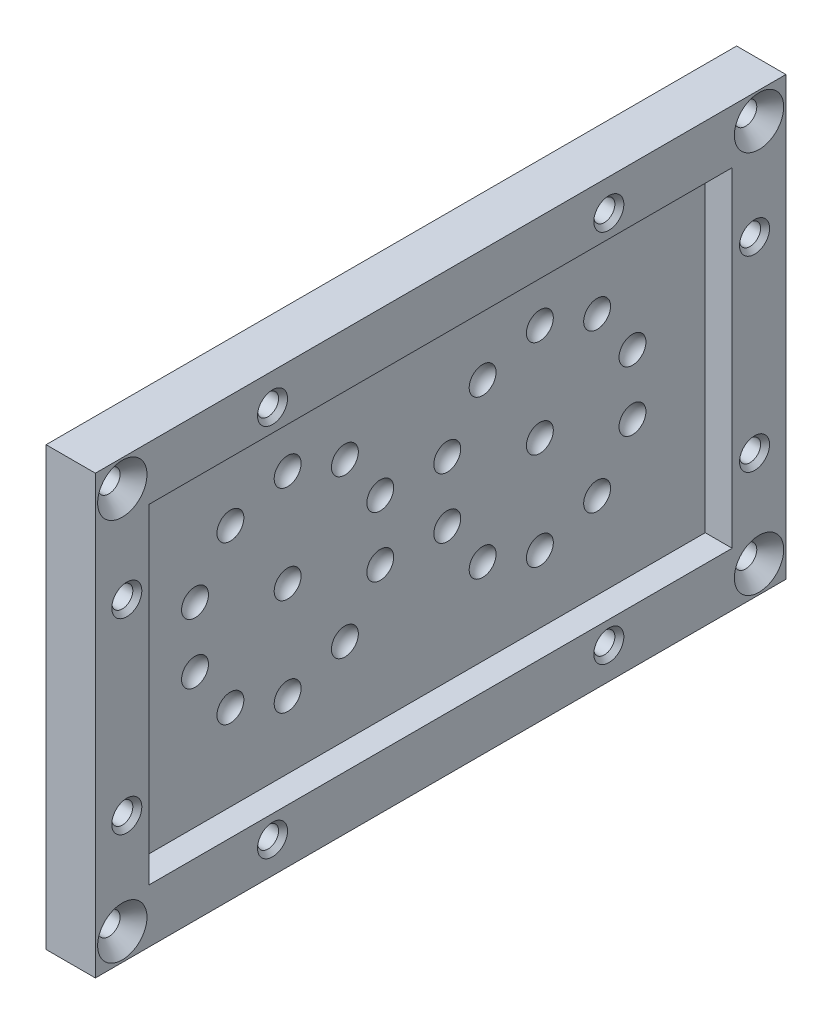
SolidWorks part; units mm, degrees
ref_plane "Front Plane" through (0, 0, 0) normal (0, 0, 1) x (1, 0, 0)
ref_plane "Top Plane" through (0, 0, 0) normal (0, 1, 0) x (1, 0, 0)
ref_plane "Right Plane" through (0, 0, 0) normal (1, 0, 0) x (0, 0, -1)
sketch "Sketch1" plane through (0, 0, 0) normal (1, 0, 0) x (0, 0, -1)
  line L1 (-65, 36.75) -> (65, 36.75)
  line L2 (-65, 36.75) -> (-65, -36.75)
  line L3 (-65, -36.75) -> (65, -36.75)
  line L4 (65, 36.75) -> (65, -36.75)
  line L5 (-65, 36.75) -> (65, -36.75) construction
  line L6 (-65, -36.75) -> (65, 36.75) construction
  point P0 (0, 0)
  dimension "D1" = 130
  dimension "D2" = 73.5
extrude "Boss-Extrude1" add sketch "Sketch1" along normal blind 5 contours L2 L1 L4 L3
sketch "Sketch2" plane through (5, 0, 0) normal (1, 0, 0) x (0, 0, -1)
  line L0 (0, 0) -> (56.25, 0) construction
  line L1 (0, 0) -> (0, 14.8929) construction
  line L12 (-57.5, -29.25) -> (57.5, -29.25) construction
  line L13 (57.5, -29.25) -> (57.5, 29.25) construction
  line L14 (57.5, 29.25) -> (-57.5, 29.25) construction
  line L15 (-57.5, 29.25) -> (-57.5, -29.25) construction
  circle A22 centre (28.125, 0) radius 21.718 construction
  circle A23 centre (28.125, -21.718) radius 3
  circle A24 centre (15.3595, -17.5702) radius 3
  circle A25 centre (7.47, -6.7112) radius 3
  circle A26 centre (7.47, 6.7112) radius 3
  circle A27 centre (15.3595, 17.5702) radius 3
  circle A28 centre (28.125, 21.718) radius 3
  circle A29 centre (40.8905, 17.5702) radius 3
  circle A30 centre (48.78, 6.7112) radius 3
  circle A31 centre (48.78, -6.7112) radius 3
  circle A32 centre (40.8905, -17.5702) radius 3
  circle A33 centre (-7.47, -6.7112) radius 3
  circle A34 centre (-15.3595, -17.5702) radius 3
  circle A35 centre (-28.125, -21.718) radius 3
  circle A36 centre (-40.8905, -17.5702) radius 3
  circle A37 centre (-48.78, -6.7112) radius 3
  circle A38 centre (-48.78, 6.7112) radius 3
  circle A39 centre (-40.8905, 17.5702) radius 3
  circle A40 centre (-28.125, 21.718) radius 3
  circle A41 centre (-15.3595, 17.5702) radius 3
  circle A42 centre (-7.47, 6.7112) radius 3
  circle A43 centre (28.125, 0) radius 3
  circle A44 centre (-28.125, 0) radius 3
  point P31 (28.125, 0)
  dimension "D2" = 43.436
  dimension "D3" = 6
  dimension "D4" = 10
  dimension "D5" = 6
  dimension "D1" = 56.25
extrude "Cut-Extrude1" cut sketch "Sketch2" against normal blind 2
fillet "Fillet1" radius 3.23 22 edges at (3, -6.7112, -10.47) (3, -17.5702, -18.3595) (3, -21.718, -31.125) (3, -17.5702, -43.8905) (3, -6.7112, -51.78) (3, 6.7112, -51.78) (3, 17.5702, -43.8905) (3, 21.718, -31.125) (3, 17.5702, -18.3595) (3, 6.7112, -10.47) (3, 17.5702, 43.8905) (3, 6.7112, 51.78) (3, -6.7112, 51.78) (3, -17.5702, 43.8905) (3, -21.718, 31.125) (3, -17.5702, 18.3595) (3, -6.7112, 10.47) (3, 6.7112, 10.47) (3, 17.5702, 18.3595) (3, 21.718, 31.125) (3, 0, -31.125) (3, 0, 31.125)
sketch "Sketch3" plane through (0, 0, 0) normal (-1, 0, 0) x (0, 0, 1)
  line L1 (-65, -36.75) -> (-75, -36.75)
  line L2 (-65, -36.75) -> (-65, 36.75)
  line L3 (-65, 36.75) -> (-75, 36.75)
  line L4 (-75, -36.75) -> (-75, 36.75)
  line L5 (-65, -36.75) -> (-75, 36.75) construction
  line L6 (-65, 36.75) -> (-75, -36.75) construction
  line L7 (65, -36.75) -> (75, -36.75)
  line L8 (65, -36.75) -> (65, 36.75)
  line L9 (65, 36.75) -> (75, 36.75)
  line L10 (75, -36.75) -> (75, 36.75)
  line L11 (65, -36.75) -> (75, 36.75) construction
  line L12 (65, 36.75) -> (75, -36.75) construction
  line L13 (75, -36.75) -> (-75, -36.75)
  line L14 (75, -36.75) -> (75, -46.75)
  line L15 (75, -46.75) -> (-75, -46.75)
  line L16 (-75, -36.75) -> (-75, -46.75)
  line L17 (75, -36.75) -> (-75, -46.75) construction
  line L18 (75, -46.75) -> (-75, -36.75) construction
  line L19 (-75, 36.75) -> (75, 36.75)
  line L20 (-75, 36.75) -> (-75, 46.75)
  line L21 (-75, 46.75) -> (75, 46.75)
  line L22 (75, 36.75) -> (75, 46.75)
  line L23 (-75, 36.75) -> (75, 46.75) construction
  line L24 (-75, 46.75) -> (75, 36.75) construction
  point P4 (-70, 0)
  point P10 (70, 0)
  point P14 (0, -41.75)
  point P17 (0, 41.75)
  line M6 (-65, -36.75) -> (65, -36.75)
  line M7 (65, -36.75) -> (65, 36.75)
  line M8 (65, 36.75) -> (-65, 36.75)
  line M9 (-65, 36.75) -> (-65, -36.75)
  dimension "D1" = 10
  dimension "D2" = 10
  dimension "D3" = 10
  dimension "D4" = 10
extrude "Boss-Extrude2" add sketch "Sketch3" against normal blind 11 contours L9 L22 L21 L20 L3 M8 | L7 L10 L9 M7 | L1 L16 L15 L14 L7 M6 | L4 L1 L3 M9 region at (0, -41.75, 0) region at (0, 0, -70) region at (0, 41.75, 0) region at (0, 0, 70)
sketch "Sketch4" plane through (11, 0, 0) normal (1, 0, 0) x (0, 0, -1)
  line L0 (0, 0) -> (0, 36.75) construction
  line L1 (65, 36.75) -> (-65, 36.75) construction
  line L2 (0, 36.75) -> (0, 46.75) construction
  line L3 (75, 46.75) -> (-75, 46.75) construction
  line L4 (0, 41.75) -> (75, 41.75) construction
  line L5 (75, -46.75) -> (75, 46.75) construction
  line L6 (0, 0) -> (65, 0) construction
  line L7 (65, 0) -> (75, 0) construction
  line L8 (65, 36.75) -> (65, -36.75) construction
  line L9 (70, 0) -> (70, 41.75) construction
  line L10 (0, -36.75) -> (0, -46.75) construction
  line L11 (-65, -36.75) -> (65, -36.75) construction
  line L12 (-75, -46.75) -> (75, -46.75) construction
  line L13 (0, 41.75) -> (-75, 41.75) construction
  line L14 (-75, -46.75) -> (-75, 46.75) construction
  line L15 (0, -41.75) -> (75, -41.75) construction
  line L16 (70, 0) -> (70, -41.75) construction
  circle A0 centre (-37.5, 41.75) radius 2.35
  circle A1 centre (37.5, 41.75) radius 2.35
  circle A2 centre (70, 20.875) radius 2.35
  circle A4 centre (37.5, -41.75) radius 2.35
  circle A5 centre (-37.5, -41.75) radius 2.35
  circle A6 centre (-70, 20.875) radius 2.35
  circle A7 centre (70, -20.875) radius 2.35
  circle A8 centre (-70, -20.875) radius 2.35
  dimension "D1" = 4.7
  dimension "D2" = 4.7
  dimension "D3" = 4.7
  dimension "D4" = 4.7
extrude "Cut-Extrude2" cut sketch "Sketch4" against normal blind 8
chamfer "Chamfer1" distance 1 angle 45 8 edges at (11, 41.75, 35.15) (11, 41.75, -39.85) (11, 20.875, -72.35) (11, -20.875, -72.35) (11, -41.75, -35.15) (11, -41.75, 39.85) (11, -20.875, 72.35) (11, 20.875, 72.35)
sketch "Sketch5" plane through (0, -46.75, 0) normal (0, -1, 0) x (1, 0, 0)
  line L1 (11, 75) -> (0, 75)
  line L2 (11, 75) -> (11, -75)
  line L3 (11, -75) -> (0, -75)
  line L4 (0, 75) -> (0, -75)
  line L5 (11, 75) -> (0, -75) construction
  line L6 (11, -75) -> (0, 75) construction
  point P4 (5.5, 0)
extrude "Boss-Extrude3" add sketch "Sketch5" along normal blind 2
sketch "Sketch6" plane through (0, 46.75, 0) normal (0, 1, 0) x (1, 0, 0)
  line L1 (0, -75) -> (11, -75)
  line L2 (0, -75) -> (0, 75)
  line L3 (0, 75) -> (11, 75)
  line L4 (11, -75) -> (11, 75)
  line L5 (0, -75) -> (11, 75) construction
  line L6 (0, 75) -> (11, -75) construction
  point P4 (5.5, 0)
extrude "Boss-Extrude4" add sketch "Sketch6" along normal blind 2
sketch "Sketch7" plane through (0, 0, 75) normal (0, 0, 1) x (1, 0, 0)
  line L1 (0, -48.75) -> (11, -48.75)
  line L2 (0, -48.75) -> (0, 48.75)
  line L3 (0, 48.75) -> (11, 48.75)
  line L4 (11, -48.75) -> (11, 48.75)
  line L5 (0, -48.75) -> (11, 48.75) construction
  line L6 (0, 48.75) -> (11, -48.75) construction
  point P4 (5.5, 0)
extrude "Boss-Extrude5" add sketch "Sketch7" along normal blind 2
sketch "Sketch8" plane through (0, 0, -75) normal (0, 0, -1) x (-1, 0, 0)
  line L1 (-11, -48.75) -> (0, -48.75)
  line L2 (-11, -48.75) -> (-11, 48.75)
  line L3 (-11, 48.75) -> (0, 48.75)
  line L4 (0, -48.75) -> (0, 48.75)
  line L5 (-11, -48.75) -> (0, 48.75) construction
  line L6 (-11, 48.75) -> (0, -48.75) construction
  point P4 (-5.5, 0)
extrude "Boss-Extrude6" add sketch "Sketch8" along normal blind 2
sketch "Sketch12" plane through (11, 0, 0) normal (1, 0, 0) x (0, 0, -1)
  line L0 (0, 0) -> (0, 48.75) construction
  line L1 (77, 48.75) -> (65, 48.75) construction
  line L2 (77, 48.75) -> (77, 36.75) construction
  line L3 (77, 36.75) -> (65, 36.75) construction
  line L4 (65, 48.75) -> (65, 36.75) construction
  line L5 (77, 48.75) -> (65, 36.75) construction
  line L6 (77, 36.75) -> (65, 48.75) construction
  line L7 (-77, 48.75) -> (77, 48.75) construction
  line L8 (0, 0) -> (77, 0) construction
  line L9 (77, 48.75) -> (77, -48.75) construction
  circle A0 centre (71, 42.75) radius 2.5
  circle A1 centre (-71, 42.75) radius 2.5
  circle A2 centre (71, -42.75) radius 2.5
  circle A3 centre (-71, -42.75) radius 2.5
  point P4 (71, 42.75)
  dimension "D1" = 5
extrude "Cut-Extrude3" cut sketch "Sketch12" against normal through all
chamfer "Chamfer2" distance 3 angle 45 4 edges at (11, -42.75, -68.5) (11, -42.75, 68.5) (11, 42.75, 73.5) (11, 42.75, -73.5)
